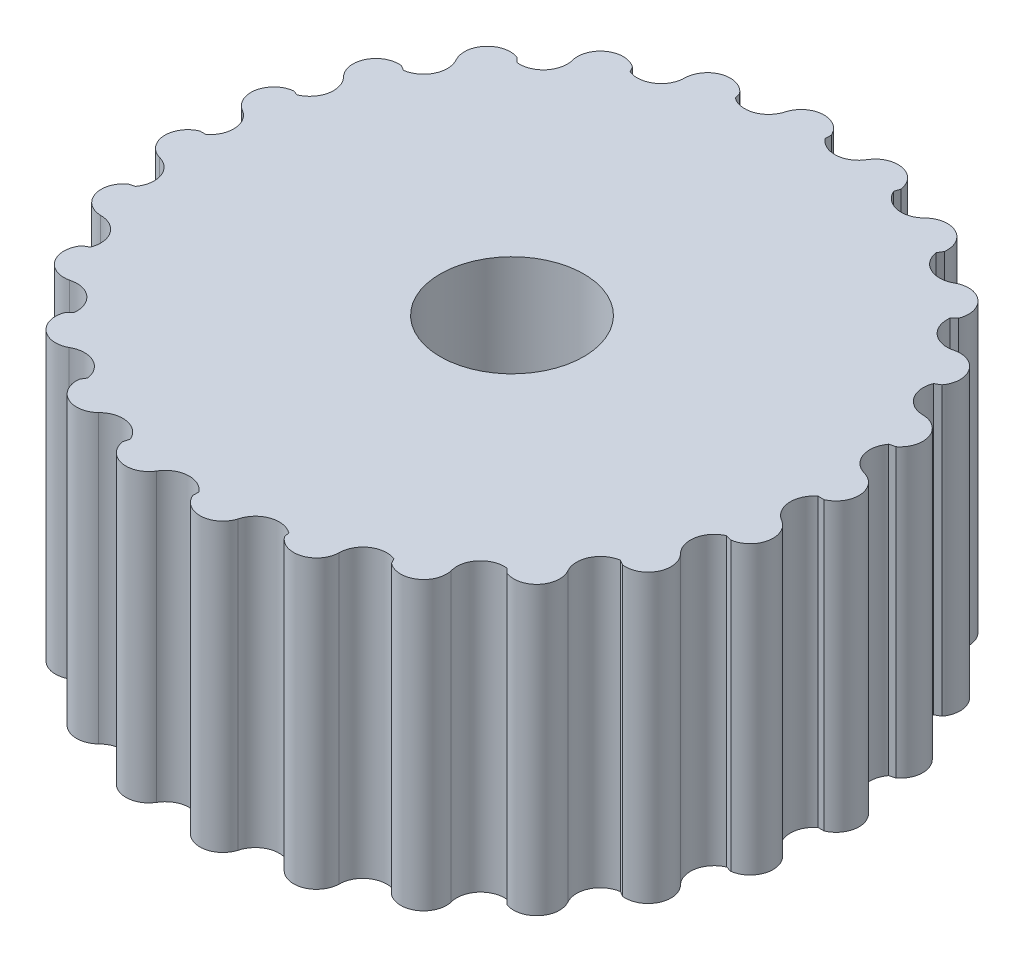
SolidWorks part; units mm, degrees
note: '?' marks a value the reader was unsure of.
ref_plane "Front Plane" through (0, 0, 0) normal (0, 0, 1) x (1, 0, 0)
ref_plane "Top Plane" through (0, 0, 0) normal (0, 1, 0) x (1, 0, 0)
ref_plane "Right Plane" through (0, 0, 0) normal (1, 0, 0) x (0, 0, -1)
sketch "Sketch1" plane through (0, 0, 0) normal (0, 1, 0) x (1, 0, 0)
  line L0 (0, 21) -> (0, 23) construction
  line L1 (2.8595, 20.8044) -> (3.1318, 22.7858) construction
  line L2 (5.6657, 20.2213) -> (6.2053, 22.1471) construction
  line L3 (0, 22) -> (0, 5)
  line L4 (1.349, 4.8146) -> (5.9355, 21.1842)
  circle A0 centre (0, 0) radius 21 construction
  arc A1 (0, 22) -> (2.9957, 21.7951) centre (1.5465, 22.6095) ccw
  arc A2 (6.2053, 22.1471) -> (0, 23) centre (0, 0) ccw construction
  arc A3 (2.9957, 21.7951) -> (5.9355, 21.1842) centre (4.3544, 20.9547) cw
  arc A4 (1.349, 4.8146) -> (0, 5) centre (0, 0) ccw
  point P6 (0, 22)
  point P9 (2.9957, 21.7951)
  dimension "D1" = 42
  dimension "D2" = 2
  dimension "D3" = 10
extrude "Boss-Extrude1" add sketch "Sketch1" along normal blind 20
pattern_circular "CirPattern1" count 24 over 360 about axis through (0, 0, 0) along (0, 1, 0) of "Boss-Extrude1"
ref_axis "Axis1" through (0, 0, 0) along (0, 1, 0)?
sketch "Sketch2" plane through (0, 20, 0) normal (0, 1, 0) x (1, 0, 0)
  line L0 (0, 74.1691) -> (0, -78.0459) construction
  line L1 (19.05, 12.7) -> (26.67, 12.7)
  line L2 (19.05, 12.7) -> (19.05, -12.7)
  line L3 (19.05, -12.7) -> (26.67, -12.7)
  line L4 (26.67, 12.7) -> (26.67, -12.7)
  line L5 (-26.67, 12.7) -> (-26.67, -12.7)
  line L6 (-19.05, -12.7) -> (-26.67, -12.7)
  line L7 (-19.05, 12.7) -> (-19.05, -12.7)
  line L8 (-19.05, 12.7) -> (-26.67, 12.7)
  point P6 (19.05, 0)
  point P12 (-19.05, 0)
  dimension "D1" = 7.62
  dimension "D2" = 25.4
  dimension "D3" = 19.05
